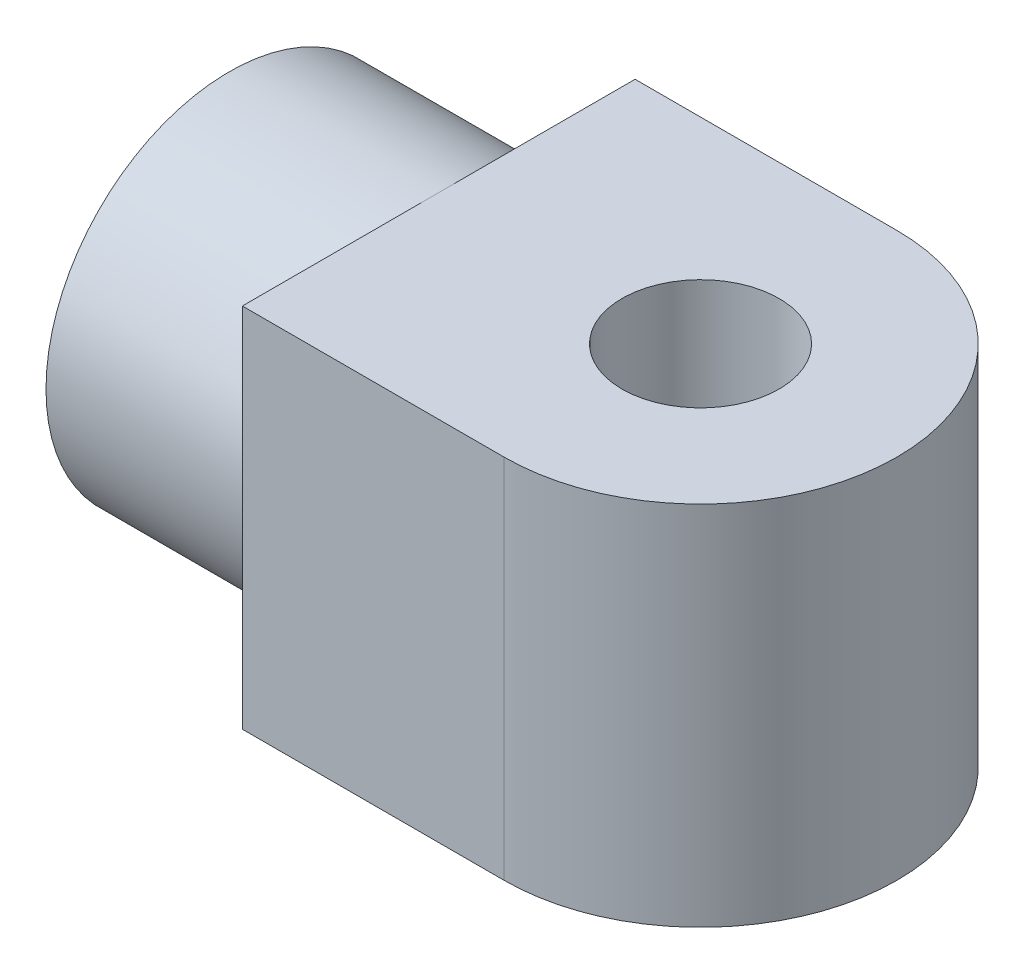
SolidWorks part; units mm, degrees
ref_plane "前视基准面" through (0, 0, 0) normal (0, 0, 1) x (1, 0, 0)
ref_plane "上视基准面" through (0, 0, 0) normal (0, 1, 0) x (1, 0, 0)
ref_plane "右视基准面" through (0, 0, 0) normal (1, 0, 0) x (0, 0, -1)
sketch "草图1" plane through (0, 0, 0) normal (0, 1, 0) x (1, 0, 0)
  line L0 (-16.348, 0) -> (16.348, 0) construction
  line L1 (0, 13.7586) -> (0, -13.7586) construction
  line L3 (-5, 7.5) -> (5, 7.5)
  line L4 (-5, 7.5) -> (-5, -7.5)
  line L5 (-5, -7.5) -> (5, -7.5)
  line L7 (-5, 7.5) -> (5, -7.5) construction
  line L8 (-5, -7.5) -> (5, 7.5) construction
  arc A0 (5, -7.5) -> (5, 7.5) centre (5, 0) ccw
  circle A1 centre (5, 0) radius 3
  point P0 (0, 0)
  point P4 (0, 0)
  point P8 (0, 0)
  point P9 (0, 0)
  dimension "D3" = 6
  dimension "D1" = 15
  dimension "D2" = 10
extrude "凸台-拉伸1" add sketch "草图1" along normal blind 14
sketch "草图2" plane through (-5, 0, 0) normal (-1, 0, 0) x (0, 0, 1)
  circle A0 centre (0, 7) radius 7
  circle A1 centre (0, 7) radius 4
  dimension "D1" = 14
  dimension "D2" = 8
extrude "凸台-拉伸2" add sketch "草图2" along normal blind 8
extrude "切除-拉伸1" cut sketch "草图2<2>" against normal blind 4 contours A1 region at (-5, 7, 0)
sketch "草图2<2>" plane through (-5, 0, 0) normal (-1, 0, 0) x (0, 0, 1) same geometry as "草图2"
